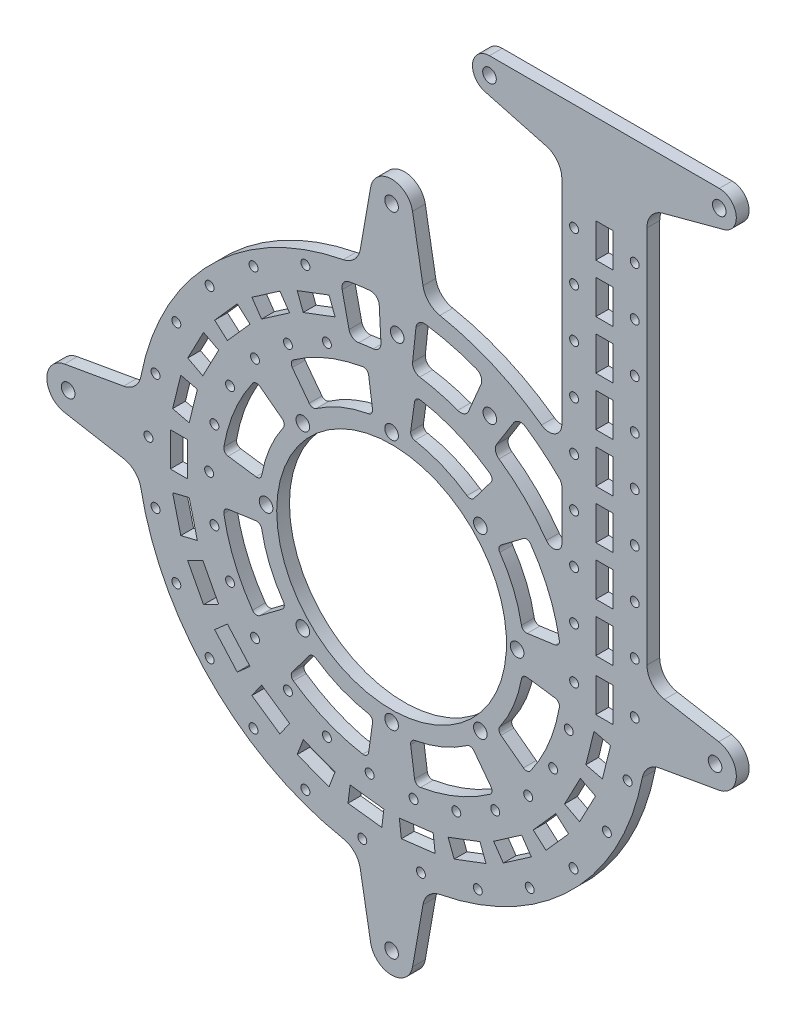
SolidWorks part; units mm, degrees
material "Thornel Mat VMA"
ref_plane "前视基准面" through (0, 0, 0) normal (0, 0, 1) x (1, 0, 0)
ref_plane "上视基准面" through (0, 0, 0) normal (0, 1, 0) x (1, 0, 0)
ref_plane "右视基准面" through (0, 0, 0) normal (1, 0, 0) x (0, 0, -1)
sketch "草图1" plane through (0, 0, 0) normal (0, 0, 1) x (1, 0, 0)
  line L1 (-100, -150) -> (100, -150)
  line L2 (-100, -150) -> (-100, 150)
  line L3 (-100, 150) -> (100, 150)
  line L4 (100, -150) -> (100, 150)
  line L5 (0, 150) -> (0, -150) construction
  line L6 (-100, 0) -> (100, 0) construction
  point P0 (0, 0)
  dimension "D1" = 200
  dimension "D2" = 300
extrude "凸台-拉伸1" add sketch "草图1" along normal blind 3
sketch "草图7" plane through (0, 0, 0) normal (0, 0, -1) x (-1, 0, 0)
  circle A0 centre (0, 0) radius 27
  dimension "D1" = 54
extrude "切除-拉伸4" cut sketch "草图7" against normal blind 10
sketch "草图3" plane through (0, 0, 0) normal (0, 0, -1) x (-1, 0, 0)
  line L1 (48, -4) -> (52, -4)
  line L2 (48, -4) -> (48, 4)
  line L3 (48, 4) -> (52, 4)
  line L4 (52, -4) -> (52, 4)
  line L5 (50, 4) -> (50, -4) construction
  line L6 (48, 0) -> (52, 0) construction
  circle A0 centre (0, 0) radius 50 construction
  point P3 (50, 0)
  dimension "D1" = 100
  dimension "D2" = 4
  dimension "D3" = 8
extrude "切除-拉伸2" cut sketch "草图3" against normal blind 10
sketch "草图5" plane through (0, 0, 3) normal (0, 0, 1) x (1, 0, 0)
  line L13 (40, 101.0647) -> (40, 50.9902)
  line L14 (7.3769, 62.9572) -> (4.924, 76.8682)
  line L15 (-4.924, 76.8682) -> (-7.3769, 62.9572)
  line L16 (-62.9572, 7.3769) -> (-76.8682, 4.924)
  line L17 (-76.8682, -4.924) -> (-62.9572, -7.3769)
  line L18 (-7.3769, -62.9572) -> (-4.924, -76.8682)
  line L19 (4.924, -76.8682) -> (7.3769, -62.9572)
  line L20 (62.9572, -7.3769) -> (76.8682, -4.924)
  line L21 (76.8682, 4.924) -> (64.1318, 7.1698)
  line L22 (60, 12.0939) -> (60, 101.0647)
  line L23 (63.7059, 105.8944) -> (78.0353, 109.7339)
  line L24 (77, 117.5976) -> (23, 117.5976)
  line L25 (21.9647, 109.7339) -> (36.2941, 105.8944)
  line L26 (40, 101.0647) -> (40, 50.9902)
  line L27 (7.3769, 62.9572) -> (4.924, 76.8682)
  line L28 (-4.924, 76.8682) -> (-7.3769, 62.9572)
  line L29 (-62.9572, 7.3769) -> (-76.8682, 4.924)
  line L30 (-76.8682, -4.924) -> (-62.9572, -7.3769)
  line L31 (-7.3769, -62.9572) -> (-4.924, -76.8682)
  line L32 (4.924, -76.8682) -> (7.3769, -62.9572)
  line L33 (62.9572, -7.3769) -> (76.8682, -4.924)
  line L34 (76.8682, 4.924) -> (64.1318, 7.1698)
  line L35 (60, 12.0939) -> (60, 101.0647)
  line L36 (63.7059, 105.8944) -> (78.0353, 109.7339)
  line L37 (77, 117.5976) -> (23, 117.5976)
  line L38 (21.9647, 109.7339) -> (36.2941, 105.8944)
  arc A20 (40, 101.0647) -> (36.2941, 105.8944) centre (35, 101.0647) ccw
  arc A21 (35.2381, 48.5621) -> (11.3547, 58.9158) centre (0, 0) ccw
  arc A22 (7.3769, 62.9572) -> (11.3547, 58.9158) centre (12.301, 63.8254) ccw
  arc A23 (4.924, 76.8682) -> (-4.924, 76.8682) centre (0, 76) ccw
  arc A24 (-11.3547, 58.9158) -> (-7.3769, 62.9572) centre (-12.301, 63.8254) ccw
  arc A25 (-11.3547, 58.9158) -> (-58.9158, 11.3547) centre (0, 0) ccw
  arc A26 (-62.9572, 7.3769) -> (-58.9158, 11.3547) centre (-63.8254, 12.301) ccw
  arc A27 (-76.8682, 4.924) -> (-76.8682, -4.924) centre (-76, 0) ccw
  arc A28 (-58.9158, -11.3547) -> (-62.9572, -7.3769) centre (-63.8254, -12.301) ccw
  arc A29 (-58.9158, -11.3547) -> (-11.3547, -58.9158) centre (0, 0) ccw
  arc A30 (-7.3769, -62.9572) -> (-11.3547, -58.9158) centre (-12.301, -63.8254) ccw
  arc A31 (-4.924, -76.8682) -> (4.924, -76.8682) centre (0, -76) ccw
  arc A32 (11.3547, -58.9158) -> (7.3769, -62.9572) centre (12.301, -63.8254) ccw
  arc A33 (11.3547, -58.9158) -> (58.9158, -11.3547) centre (0, 0) ccw
  arc A34 (62.9572, -7.3769) -> (58.9158, -11.3547) centre (63.8254, -12.301) ccw
  arc A35 (76.8682, -4.924) -> (76.8682, 4.924) centre (76, 0) ccw
  arc A36 (60, 12.0939) -> (64.1318, 7.1698) centre (65, 12.0939) ccw
  arc A37 (63.7059, 105.8944) -> (60, 101.0647) centre (65, 101.0647) ccw
  arc A38 (78.0353, 109.7339) -> (77, 117.5976) centre (77, 113.5976) ccw
  arc A39 (23, 117.5976) -> (21.9647, 109.7339) centre (23, 113.5976) ccw
  arc A40 (40, 101.0647) -> (36.2941, 105.8944) centre (35, 101.0647) ccw
  arc A41 (35.2381, 48.5621) -> (11.3547, 58.9158) centre (0, 0) ccw
  arc A42 (7.3769, 62.9572) -> (11.3547, 58.9158) centre (12.301, 63.8254) ccw
  arc A43 (4.924, 76.8682) -> (-4.924, 76.8682) centre (0, 76) ccw
  arc A44 (-11.3547, 58.9158) -> (-7.3769, 62.9572) centre (-12.301, 63.8254) ccw
  arc A45 (-11.3547, 58.9158) -> (-58.9158, 11.3547) centre (0, 0) ccw
  arc A46 (-62.9572, 7.3769) -> (-58.9158, 11.3547) centre (-63.8254, 12.301) ccw
  arc A47 (-76.8682, 4.924) -> (-76.8682, -4.924) centre (-76, 0) ccw
  arc A48 (-58.9158, -11.3547) -> (-62.9572, -7.3769) centre (-63.8254, -12.301) ccw
  arc A49 (-58.9158, -11.3547) -> (-11.3547, -58.9158) centre (0, 0) ccw
  arc A50 (-7.3769, -62.9572) -> (-11.3547, -58.9158) centre (-12.301, -63.8254) ccw
  arc A51 (-4.924, -76.8682) -> (4.924, -76.8682) centre (0, -76) ccw
  arc A52 (11.3547, -58.9158) -> (7.3769, -62.9572) centre (12.301, -63.8254) ccw
  arc A53 (11.3547, -58.9158) -> (58.9158, -11.3547) centre (0, 0) ccw
  arc A54 (62.9572, -7.3769) -> (58.9158, -11.3547) centre (63.8254, -12.301) ccw
  arc A55 (76.8682, -4.924) -> (76.8682, 4.924) centre (76, 0) ccw
  arc A56 (60, 12.0939) -> (64.1318, 7.1698) centre (65, 12.0939) ccw
  arc A57 (63.7059, 105.8944) -> (60, 101.0647) centre (65, 101.0647) ccw
  arc A58 (78.0353, 109.7339) -> (77, 117.5976) centre (77, 113.5976) ccw
  arc A59 (23, 117.5976) -> (21.9647, 109.7339) centre (23, 113.5976) ccw
  arc A82 (35.2381, 48.5621) -> (40, 50.9902) centre (37, 50.9902) ccw
  arc A83 (35.2381, 48.5621) -> (40, 50.9902) centre (37, 50.9902) ccw
  dimension "D1" = 0
extrude "切除-拉伸3" cut sketch "草图5" against normal blind 10 flip side to cut
sketch "草图8" plane through (0, 0, 0) normal (0, 0, -1) x (-1, 0, 0)
  circle A0 centre (76, 0) radius 1.6
  circle A1 centre (0, -76) radius 1.6
  circle A2 centre (-76, 0) radius 1.6
  circle A3 centre (0, 76) radius 1.6
  circle A4 centre (-23, 113.5976) radius 1.6
  circle A5 centre (-77, 113.5976) radius 1.6
  dimension "D1" = 3.2
extrude "切除-拉伸5" cut sketch "草图8" against normal blind 10
sketch "草图9" plane through (0, 0, 0) normal (0, 0, -1) x (-1, 0, 0)
  line L0 (31.8645, 4.4783) -> (38.404, 5.3973) construction
  line L1 (30.9722, 23.3393) -> (25.6982, 19.365) construction
  line L2 (31.8645, 4.4783) -> (38.404, 5.3973)
  line L3 (30.9722, 23.3393) -> (25.6982, 19.365)
  circle A0 centre (29.5, 0) radius 1.6 construction
  arc A1 (30.5162, 5.4554) -> (31.8645, 4.4783) centre (31.6975, 5.6666) ccw construction
  arc A2 (38.404, 5.3973) -> (39.4196, 6.7893) centre (38.237, 6.5857) ccw construction
  arc A3 (39.4196, 6.7893) -> (32.6747, 23.0731) centre (0, 0) ccw construction
  arc A4 (32.6747, 23.0731) -> (30.9722, 23.3393) centre (31.6944, 22.3809) ccw construction
  arc A5 (25.6982, 19.365) -> (25.4358, 17.7207) centre (26.4204, 18.4066) ccw construction
  arc A6 (30.5162, 5.4554) -> (25.4358, 17.7207) centre (0, 0) ccw construction
  circle A7 centre (29.5, 0) radius 1.6
  arc A8 (30.5162, 5.4554) -> (31.8645, 4.4783) centre (31.6975, 5.6666) ccw
  arc A9 (38.404, 5.3973) -> (39.4196, 6.7893) centre (38.237, 6.5857) ccw
  arc A10 (39.4196, 6.7893) -> (32.6747, 23.0731) centre (0, 0) ccw
  arc A11 (32.6747, 23.0731) -> (30.9722, 23.3393) centre (31.6944, 22.3809) ccw
  arc A12 (25.6982, 19.365) -> (25.4358, 17.7207) centre (26.4204, 18.4066) ccw
  arc A13 (30.5162, 5.4554) -> (25.4358, 17.7207) centre (0, 0) ccw
pattern_circular "阵列(圆周)1" count 26 over 360 about axis through (0, 0, 0) along (0, 0, -1) skipping 10, 11, 12 of "切除-拉伸2"
extrude "切除-拉伸6" cut sketch "草图9" against normal blind 10
pattern_circular "阵列(圆周)2" count 8 over 360 about axis through (0, 0, 0) along (0, 0, -1) of "切除-拉伸6"
sketch "草图11" plane through (0, 0, 0) normal (0, 0, -1) x (-1, 0, 0)
  line L4 (-48, 8) -> (-52, 8)
  line L5 (-48, 16) -> (-48, 8)
  line L6 (-52, 16) -> (-48, 16)
  line L7 (-52, 8) -> (-52, 16)
  line L9 (-48, -4) -> (-48, 4) construction
  line L10 (-48, 4) -> (-52, 4) construction
  dimension "D1" = 4
  dimension "D2" = 4
  dimension "D3" = 8
extrude "切除-拉伸7" cut sketch "草图11" against normal blind 10
pattern_linear "阵列(线性)1" count 8 spacing 11.5 along (0, 1, 0) of "切除-拉伸7"
sketch "草图12" plane through (0, 0, 3) normal (0, 0, 1) x (1, 0, 0)
  line L0 (0, 60) -> (0, 0) construction
  line L1 (-9.6769, 38.8118) -> (-14.5153, 58.2177)
  line L2 (26.2424, 30.1884) -> (39.3635, 45.2826)
  arc A0 (26.2424, 30.1884) -> (-9.6769, 38.8118) centre (0, 0) ccw
  arc A1 (39.3635, 45.2826) -> (-14.5153, 58.2177) centre (0, 0) ccw
  dimension "D1" = 80
  dimension "D2" = 120
  dimension "D3" = 14
  dimension "D4" = 41
extrude "凸台-拉伸2" add sketch "草图12" against normal up to surface (3 mm away) up to face at (50, 23.5, 0)
sketch "草图13" plane through (0, 0, 3) normal (0, 0, 1) x (1, 0, 0)
  line L0 (0, 0) -> (42.875, 0) construction
  line L1 (42.875, 0) -> (57.125, 0) construction
  circle A2 centre (42.875, 0) radius 1.05
  circle A3 centre (57.125, 0) radius 1.05
  dimension "D3" = 2.1
  dimension "D1" = 42.875
  dimension "D2" = 14.25
extrude "切除-拉伸8" cut sketch "草图13" against normal blind 10
pattern_circular "阵列(圆周)3" count 26 over 360 about axis through (0, 0, 3) along (0, 0, -1) skipping 19, 20, 21, 22, 23, 24, 25 of "切除-拉伸8"
sketch "草图14" plane through (0, 0, 3) normal (0, 0, 1) x (1, 0, 0)
  line L0 (50, 16) -> (50, 12.0045) construction
  line L1 (48, 16) -> (52, 16) construction
  line L2 (50, 12.0045) -> (57.125, 12.0045) construction
  circle A0 centre (57.125, 12.0045) radius 1.05
  circle A1 centre (57.125, 0) radius 1.05 construction
  circle A2 centre (42.875, 12.0045) radius 1.05
  dimension "D1" = 3.9955
  dimension "D2" = 14.25
extrude "切除-拉伸9" cut sketch "草图14" against normal blind 10
pattern_linear "阵列(线性)2" count 8 spacing 11.5 along (0, 1, 0) of "切除-拉伸9"
sketch "草图15" plane through (0, 0, 0) normal (0, 0, -1) x (-1, 0, 0)
  circle A0 centre (-1.3088, 49.9829) radius 1.6 construction
  circle A1 centre (-23.0874, 44.3505) radius 1.6 construction
  circle A2 centre (-1.3088, 49.9829) radius 1.6
  circle A3 centre (-23.0874, 44.3505) radius 1.6
extrude "切除-拉伸10" cut sketch "草图15" against normal blind 10
sketch "草图16" plane through (0, 0, 3) normal (0, 0, 1) x (1, 0, 0)
  line L0 (4.7199, 44.249) -> (5.9397, 55.6841)
  line L1 (17.3242, 40.9893) -> (21.8012, 51.582)
  line L2 (-2.3976, 44.4354) -> (-3.0173, 55.9187)
  line L3 (-9.582, 43.4561) -> (-12.0583, 54.6864)
  line L4 (0, 44.5) -> (0, 56) construction
  arc A0 (17.3242, 40.9893) -> (4.7199, 44.249) centre (0, 0) ccw
  arc A1 (21.8012, 51.582) -> (5.9397, 55.6841) centre (0, 0) ccw
  arc A2 (35.2381, 48.5621) -> (11.3547, 58.9158) centre (0, 0) ccw construction
  arc A3 (23.0731, 32.6747) -> (6.7893, 39.4196) centre (0, 0) ccw construction
  arc A4 (-2.3976, 44.4354) -> (-9.582, 43.4561) centre (0, 0) ccw
  circle A5 centre (1.3088, 49.9829) radius 1.6 construction
  circle A6 centre (23.0874, 44.3505) radius 1.6 construction
  arc A7 (-3.0173, 55.9187) -> (-12.0583, 54.6864) centre (0, 0) ccw
  dimension "D1" = 4
  dimension "D2" = 4.5
  dimension "D3" = 4
  dimension "D4" = 4
  dimension "D5" = 3
  dimension "D6" = 4
extrude "切除-拉伸11" cut sketch "草图16" against normal blind 10
sketch "草图17" plane through (0, 0, 3) normal (0, 0, 1) x (1, 0, 0)
  line L0 (40, 39.1918) -> (40, 19.5)
  line L1 (23.6397, 37.7016) -> (29.7489, 47.4448)
  line L2 (40, 101.0647) -> (40, 50.9902) construction
  arc A0 (40, 19.5) -> (23.6397, 37.7016) centre (0, 0) ccw
  circle A2 centre (23.0874, 44.3505) radius 1.6 construction
  arc A3 (40, 39.1918) -> (29.7489, 47.4448) centre (0, 0) ccw
  dimension "D1" = 89
  dimension "D2" = 4
  dimension "D3" = 112
extrude "切除-拉伸12" cut sketch "草图17" against normal blind 10
fillet "圆角1" radius 2 12 edges at (-9.582, 43.4561, 1.5) (-12.0583, 54.6864, 1.5) (-3.0173, 55.9187, 1.5) (-2.3976, 44.4354, 1.5) (4.7199, 44.249, 1.5) (5.9397, 55.6841, 1.5) (21.8012, 51.582, 1.5) (17.3242, 40.9893, 1.5) (23.6397, 37.7016, 1.5) (40, 19.5, 1.5) (40, 39.1918, 1.5) (29.7489, 47.4448, 1.5)
